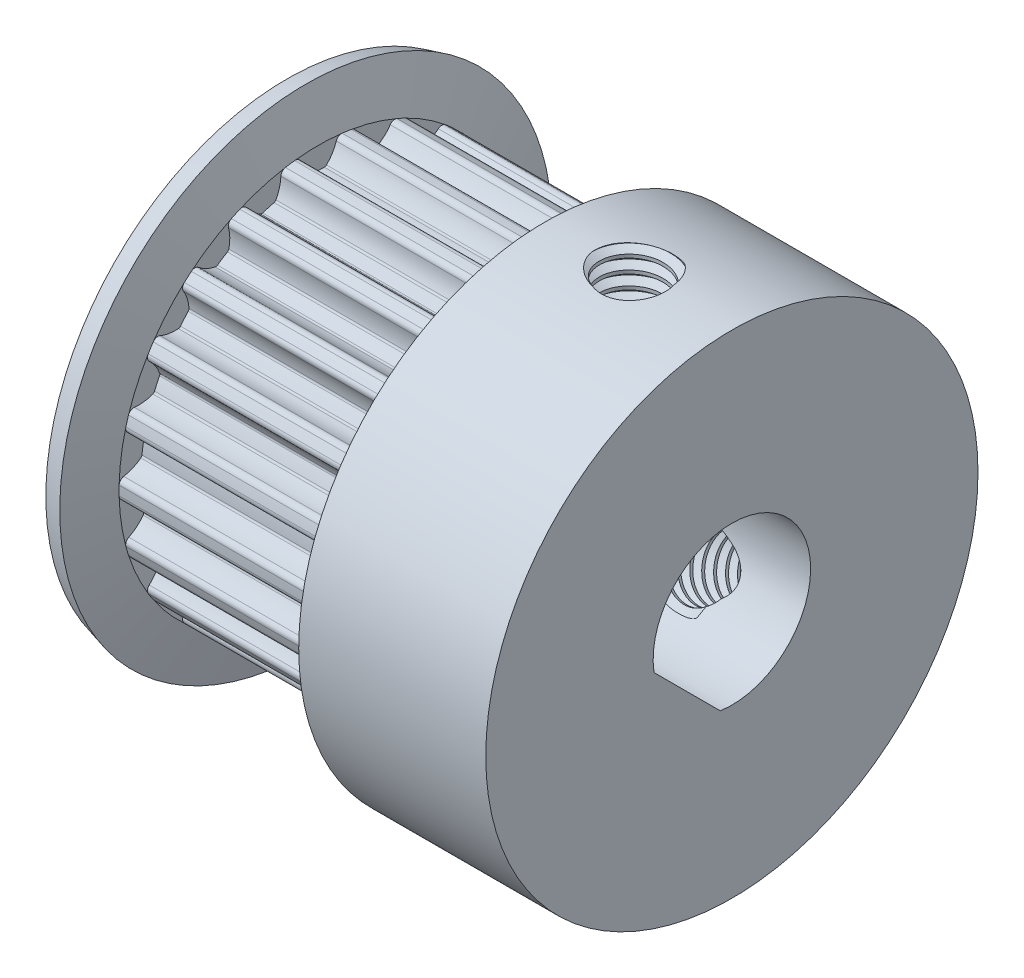
SolidWorks part; units mm, degrees
ref_plane "Front Plane" through (0, 0, 0) normal (0, 0, 1) x (1, 0, 0)
ref_plane "Top Plane" through (0, 0, 0) normal (0, 1, 0) x (1, 0, 0)
ref_plane "Right Plane" through (0, 0, 0) normal (1, 0, 0) x (0, 0, -1)
sketch "Sketch12" plane through (0, 0, 0) normal (0, 0, 1) x (1, 0, 0)
  line L0 (1, 9.9933) -> (1, 0)
  line L1 (1, 0) -> (2, 0)
  line L2 (2, 0) -> (2, 10.125)
  line L3 (2, 10.125) -> (1.3636, 12.5)
  line L4 (1.3636, 12.5) -> (0.3977, 12.2412)
  line L5 (0.3977, 12.2412) -> (1, 9.9933)
  line L6 (0.3977, 0) -> (2, 0) construction
revolve "Revolve1" add sketch "Sketch12" angle 360 about L6 reverse direction yes
other "Freeze***"
ref_plane "Plane4" through (2, 0, 0) normal (1, 0, 0) x (0, 0, -1)
sketch "Sketch16" plane through (2, 0, 0) normal (1, 0, 0) x (0, 0, -1)
  arc A0 (0.963, 10.0791) -> (1.9156, 9.9421) centre (0, 0) cw
  arc A1 (1.9156, 9.9421) -> (2.1887, 8.7453) centre (3.8823, 9.7613) ccw
  arc A2 (2.1887, 8.7453) -> (2.8868, 8.5403) centre (0, 0) cw
  arc A3 (2.8868, 8.5403) -> (3.7636, 9.3995) centre (2.0113, 10.3107) ccw
  arc A4 (3.7636, 9.3995) -> (4.6391, 8.9997) centre (0, 0) cw
  arc A5 (4.6391, 8.9997) -> (4.5639, 7.7744) centre (6.4751, 8.2721) ccw
  arc A6 (4.5639, 7.7744) -> (5.1759, 7.3811) centre (0, 0) cw
  arc A7 (5.1759, 7.3811) -> (6.2593, 7.9584) centre (4.8347, 9.3263) ccw
  arc A8 (6.2593, 7.9584) -> (6.9867, 7.3282) centre (0, 0) cw
  arc A9 (6.9867, 7.3282) -> (6.5693, 6.1737) centre (8.5434, 6.1128) ccw
  arc A10 (6.5693, 6.1737) -> (7.0458, 5.6238) centre (0, 0) cw
  arc A11 (7.0458, 5.6238) -> (8.2479, 5.8726) centre (7.2664, 7.5865) ccw
  arc A12 (8.2479, 5.8726) -> (8.7682, 5.063) centre (0, 0) cw
  arc A13 (8.7682, 5.063) -> (8.0425, 4.0728) centre (9.9195, 3.4582) ccw
  arc A14 (8.0425, 4.0728) -> (8.3448, 3.411) centre (0, 0) cw
  arc A15 (8.3448, 3.411) -> (9.5683, 3.311) centre (9.1094, 5.232) ccw
  arc A16 (9.5683, 3.311) -> (9.8395, 2.3876) centre (0, 0) cw
  arc A17 (9.8395, 2.3876) -> (8.8642, 1.642) centre (10.4919, 0.5235) ccw
  arc A18 (8.8642, 1.642) -> (8.9677, 0.9218) centre (0, 0) cw
  arc A19 (8.9677, 0.9218) -> (10.1136, 0.4812) centre (10.2144, 2.4536) ccw
  arc A20 (10.1136, 0.4812) -> (10.1136, -0.4812) centre (0, 0) cw
  arc A21 (10.1136, -0.4812) -> (8.9677, -0.9218) centre (10.2144, -2.4536) ccw
  arc A22 (8.9677, -0.9218) -> (8.8642, -1.642) centre (0, 0) cw
  arc A23 (8.8642, -1.642) -> (9.8395, -2.3876) centre (10.4919, -0.5235) ccw
  arc A24 (9.8395, -2.3876) -> (9.5683, -3.311) centre (0, 0) cw
  arc A25 (9.5683, -3.311) -> (8.3448, -3.411) centre (9.1094, -5.232) ccw
  arc A26 (8.3448, -3.411) -> (8.0425, -4.0728) centre (0, 0) cw
  arc A27 (8.0425, -4.0728) -> (8.7682, -5.063) centre (9.9195, -3.4582) ccw
  arc A28 (8.7682, -5.063) -> (8.2479, -5.8726) centre (0, 0) cw
  arc A29 (8.2479, -5.8726) -> (7.0458, -5.6238) centre (7.2664, -7.5865) ccw
  arc A30 (7.0458, -5.6238) -> (6.5693, -6.1737) centre (0, 0) cw
  arc A31 (6.5693, -6.1737) -> (6.9867, -7.3282) centre (8.5434, -6.1128) ccw
  arc A32 (6.9867, -7.3282) -> (6.2593, -7.9584) centre (0, 0) cw
  arc A33 (6.2593, -7.9584) -> (5.1759, -7.3811) centre (4.8347, -9.3263) ccw
  arc A34 (5.1759, -7.3811) -> (4.5639, -7.7744) centre (0, 0) cw
  arc A35 (4.5639, -7.7744) -> (4.6391, -8.9997) centre (6.4751, -8.2721) ccw
  arc A36 (4.6391, -8.9997) -> (3.7636, -9.3995) centre (0, 0) cw
  arc A37 (3.7636, -9.3995) -> (2.8868, -8.5403) centre (2.0113, -10.3107) ccw
  arc A38 (2.8868, -8.5403) -> (2.1887, -8.7453) centre (0, 0) cw
  arc A39 (2.1887, -8.7453) -> (1.9156, -9.9421) centre (3.8823, -9.7613) ccw
  arc A40 (1.9156, -9.9421) -> (0.963, -10.0791) centre (0, 0) cw
  arc A41 (0.963, -10.0791) -> (0.3638, -9.0077) centre (-0.975, -10.4597) ccw
  arc A42 (0.3638, -9.0077) -> (-0.3638, -9.0077) centre (0, 0) cw
  arc A43 (-0.3638, -9.0077) -> (-0.963, -10.0791) centre (0.975, -10.4597) ccw
  arc A44 (-0.963, -10.0791) -> (-1.9156, -9.9421) centre (0, 0) cw
  arc A45 (-1.9156, -9.9421) -> (-2.1887, -8.7453) centre (-3.8823, -9.7613) ccw
  arc A46 (-2.1887, -8.7453) -> (-2.8868, -8.5403) centre (0, 0) cw
  arc A47 (-2.8868, -8.5403) -> (-3.7636, -9.3995) centre (-2.0113, -10.3107) ccw
  arc A48 (-3.7636, -9.3995) -> (-4.6391, -8.9997) centre (0, 0) cw
  arc A49 (-4.6391, -8.9997) -> (-4.5639, -7.7744) centre (-6.4751, -8.2721) ccw
  arc A50 (-4.5639, -7.7744) -> (-5.1759, -7.3811) centre (0, 0) cw
  arc A51 (-5.1759, -7.3811) -> (-6.2593, -7.9584) centre (-4.8347, -9.3263) ccw
  arc A52 (-6.2593, -7.9584) -> (-6.9867, -7.3282) centre (0, 0) cw
  arc A53 (-6.9867, -7.3282) -> (-6.5693, -6.1737) centre (-8.5434, -6.1128) ccw
  arc A54 (-6.5693, -6.1737) -> (-7.0458, -5.6238) centre (0, 0) cw
  arc A55 (-7.0458, -5.6238) -> (-8.2479, -5.8726) centre (-7.2664, -7.5865) ccw
  arc A56 (-8.2479, -5.8726) -> (-8.7682, -5.063) centre (0, 0) cw
  arc A57 (-8.7682, -5.063) -> (-8.0425, -4.0728) centre (-9.9195, -3.4582) ccw
  arc A58 (-8.0425, -4.0728) -> (-8.3448, -3.411) centre (0, 0) cw
  arc A59 (-8.3448, -3.411) -> (-9.5683, -3.311) centre (-9.1094, -5.232) ccw
  arc A60 (-9.5683, -3.311) -> (-9.8395, -2.3876) centre (0, 0) cw
  arc A61 (-9.8395, -2.3876) -> (-8.8642, -1.642) centre (-10.4919, -0.5235) ccw
  arc A62 (-8.8642, -1.642) -> (-8.9677, -0.9218) centre (0, 0) cw
  arc A63 (-8.9677, -0.9218) -> (-10.1136, -0.4812) centre (-10.2144, -2.4536) ccw
  arc A64 (-10.1136, -0.4812) -> (-10.1136, 0.4812) centre (0, 0) cw
  arc A65 (-10.1136, 0.4812) -> (-8.9677, 0.9218) centre (-10.2144, 2.4536) ccw
  arc A66 (-8.9677, 0.9218) -> (-8.8642, 1.642) centre (0, 0) cw
  arc A67 (-8.8642, 1.642) -> (-9.8395, 2.3876) centre (-10.4919, 0.5235) ccw
  arc A68 (-9.8395, 2.3876) -> (-9.5683, 3.311) centre (0, 0) cw
  arc A69 (-9.5683, 3.311) -> (-8.3448, 3.411) centre (-9.1094, 5.232) ccw
  arc A70 (-8.3448, 3.411) -> (-8.0425, 4.0728) centre (0, 0) cw
  arc A71 (-8.0425, 4.0728) -> (-8.7682, 5.063) centre (-9.9195, 3.4582) ccw
  arc A72 (-8.7682, 5.063) -> (-8.2479, 5.8726) centre (0, 0) cw
  arc A73 (-8.2479, 5.8726) -> (-7.0458, 5.6238) centre (-7.2664, 7.5865) ccw
  arc A74 (-7.0458, 5.6238) -> (-6.5693, 6.1737) centre (0, 0) cw
  arc A75 (-6.5693, 6.1737) -> (-6.9867, 7.3282) centre (-8.5434, 6.1128) ccw
  arc A76 (-6.9867, 7.3282) -> (-6.2593, 7.9584) centre (0, 0) cw
  arc A77 (-6.2593, 7.9584) -> (-5.1759, 7.3811) centre (-4.8347, 9.3263) ccw
  arc A78 (-5.1759, 7.3811) -> (-4.5639, 7.7744) centre (0, 0) cw
  arc A79 (-4.5639, 7.7744) -> (-4.6391, 8.9997) centre (-6.4751, 8.2721) ccw
  arc A80 (-4.6391, 8.9997) -> (-3.7636, 9.3995) centre (0, 0) cw
  arc A81 (-3.7636, 9.3995) -> (-2.8868, 8.5403) centre (-2.0113, 10.3107) ccw
  arc A82 (-2.8868, 8.5403) -> (-2.1887, 8.7453) centre (0, 0) cw
  arc A83 (-2.1887, 8.7453) -> (-1.9156, 9.9421) centre (-3.8823, 9.7613) ccw
  arc A84 (-1.9156, 9.9421) -> (-0.963, 10.0791) centre (0, 0) cw
  arc A85 (-0.963, 10.0791) -> (-0.3638, 9.0077) centre (0.975, 10.4597) ccw
  arc A86 (-0.3638, 9.0077) -> (0.3638, 9.0077) centre (0, 0) cw
  arc A87 (0.3638, 9.0077) -> (0.963, 10.0791) centre (-0.975, 10.4597) ccw
extrude "Boss-Extrude4" add sketch "Sketch16" along normal blind 11
ref_plane "Plane5" through (13, 0, 0) normal (-1, 0, 0) x (0, 0, 1)
sketch "Sketch21" plane through (13, 0, 0) normal (-1, 0, 0) x (0, 0, 1)
  circle A0 centre (0, 0) radius 12.5
extrude "Boss-Extrude5" add sketch "Sketch21" against normal blind 10
sketch "Sketch22" plane through (1, 0, 0) normal (-1, 0, 0) x (0, 0, 1)
  circle A0 centre (0, 0) radius 8
extrude "Boss-Extrude6" add sketch "Sketch22" along normal blind 1
hole_wizard "Ø8.0 (8) Diameter Hole2" positions "Sketch24" profile "Sketch23" hole size "Ø8.0" standard "ANSI Metric"
sketch "Sketch24" plane through (23, 0, 0) normal (1, 0, 0) x (0, 0, -1)
  point P0 (0, 0)
sketch "Sketch23" plane through (23, 0, 0) normal (0, 1, 0) x (0, 0, -1)
  line L0 (0, 0) -> (0, 23)
  line L1 (0, 23) -> (4, 23)
  line L2 (4, 23) -> (4, 0)
  line L5 (4, 0) -> (0, 0)
  line L11 (0, -6.35) -> (0, 107.95) construction
  dimension "Thru Hole Dia." = 8
  dimension "Thru Hole Depth" = 23
ref_plane "Plane6" through (0, -1.8284, -3.1669) normal (0, 0.5, 0.866) x (1, 0, 0)
hole_wizard "M3 Clearance Hole3" positions "Sketch26" profile "Sketch25" hole size "M3" standard "ANSI Metric"
sketch "Sketch26" plane through (0, -1.8284, -3.1669) normal (0, 0.5, 0.866) x (1, 0, 0)
  point P0 (18, 0)
sketch "Sketch25" plane through (18, -1.8284, -3.1669) normal (1, 0, 0) x (0, -0.866, 0.5)
  line L0 (0, 0) -> (0, 13.4185)
  line L1 (0, 13.4185) -> (1.621, 13.4185)
  line L2 (1.621, 13.4185) -> (1.621, 0)
  line L5 (1.621, 0) -> (0, 0)
  line L11 (0, -6.35) -> (0, 107.95) construction
  dimension "Thru Hole Dia." = 3.242
  dimension "Thru Hole Depth" = 13.4185
ref_plane "Plane7" through (0, 3.6568, 0) normal (0, -1, 0) x (-1, 0, 0)
hole_wizard "M3 Clearance Hole4" positions "Sketch28" profile "Sketch27" hole size "M3" standard "ANSI Metric"
sketch "Sketch28" plane through (0, 3.6568, 0) normal (0, -1, 0) x (-1, 0, 0)
  point P0 (-18, 0)
sketch "Sketch27" plane through (18, 3.6568, 0) normal (1, 0, 0) x (0, 0, -1)
  line L0 (0, 0) -> (0, 8.8432)
  line L1 (0, 8.8432) -> (1.621, 8.8432)
  line L2 (1.621, 8.8432) -> (1.621, 0)
  line L5 (1.621, 0) -> (0, 0)
  line L11 (0, -6.35) -> (0, 107.95) construction
  dimension "Thru Hole Dia." = 3.242
  dimension "Thru Hole Depth" = 8.8432
chamfer "Chamfer2" distance 2 angle 14.036 1 edges at (13, 0, 12.5) first distance on face at (13, 0, 0)
fillet "Fillet3" radius 0.15 44 edges at (7.5, -7.3811, 5.1759) (7.5, -5.6238, 7.0458) (7.5, -8.5403, 2.8868) (7.5, 0.9218, 8.9677) (7.5, 0.9218, -8.9677) (7.5, 8.7453, 2.1887) (7.5, 5.6238, -7.0458) (7.5, 7.3811, -5.1759) (7.5, 1.642, -8.8642) (7.5, 8.5403, 2.8868) (7.5, -6.1737, 6.5693) (7.5, 4.0728, -8.0425) (7.5, 6.1737, -6.5693) (7.5, -3.411, -8.3448) (7.5, -7.7744, 4.5639) (7.5, -0.9218, 8.9677) (7.5, 7.7744, -4.5639) (7.5, -4.0728, -8.0425) (7.5, -8.7453, 2.1887) (7.5, -1.642, 8.8642) (7.5, -7.3811, -5.1759) (7.5, 6.1737, 6.5693) (7.5, -7.7744, -4.5639) (7.5, 3.411, -8.3448) (7.5, 4.0728, 8.0425) (7.5, 5.6238, 7.0458) (7.5, 3.411, 8.3448) (7.5, 8.7453, -2.1887) (7.5, -8.5403, -2.8868) (7.5, -5.6238, -7.0458) (7.5, -8.7453, -2.1887) (7.5, -3.411, 8.3448) (7.5, 7.7744, 4.5639) (7.5, -6.1737, -6.5693) (7.5, 7.3811, 5.1759) (7.5, -4.0728, 8.0425) (7.5, -9.0077, -0.3638) (7.5, 9.0077, -0.3638) (7.5, -9.0077, 0.3638) (7.5, 8.5403, -2.8868) (7.5, -1.642, -8.8642) (7.5, 9.0077, 0.3638) (7.5, -0.9218, -8.9677) (7.5, 1.642, 8.8642) tangent propagation no
fillet "Fillet4" radius 0.28 44 edges at (7.5, -3.311, 9.5683) (7.5, -9.9421, 1.9156) (7.5, -7.9584, 6.2593) (7.5, 9.9421, -1.9156) (7.5, -0.4812, 10.1136) (7.5, 10.0791, -0.963) (7.5, -5.8726, 8.2479) (7.5, 9.3995, -3.7636) (7.5, -9.3995, 3.7636) (7.5, 10.0791, 0.963) (7.5, 0.4812, 10.1136) (7.5, 8.9997, -4.6391) (7.5, -2.3876, 9.8395) (7.5, 9.9421, 1.9156) (7.5, -5.063, 8.7682) (7.5, 7.9584, -6.2593) (7.5, -7.3282, 6.9867) (7.5, 9.3995, 3.7636) (7.5, -8.9997, 4.6391) (7.5, 7.3282, -6.9867) (7.5, -10.0791, 0.963) (7.5, 8.9997, 4.6391) (7.5, -2.3876, -9.8395) (7.5, 5.8726, -8.2479) (7.5, -3.311, -9.5683) (7.5, 7.9584, 6.2593) (7.5, -5.063, -8.7682) (7.5, 5.063, -8.7682) (7.5, -5.8726, -8.2479) (7.5, 7.3282, 6.9867) (7.5, -7.3282, -6.9867) (7.5, 3.311, -9.5683) (7.5, -7.9584, -6.2593) (7.5, 5.8726, 8.2479) (7.5, -8.9997, -4.6391) (7.5, 2.3876, -9.8395) (7.5, -9.3995, -3.7636) (7.5, 5.063, 8.7682) (7.5, -9.9421, -1.9156) (7.5, 0.4812, -10.1136) (7.5, -10.0791, -0.963) (7.5, 3.311, 9.5683) (7.5, -0.4812, -10.1136) (7.5, 2.3876, 9.8395) tangent propagation no
ref_plane "Plane8" through (0, 12.5, 0) normal (0, 1, 0) x (1, 0, 0)
thread "Thread1" pitch 0.7 method cut profile "Thread Profile1" start angle 0, offset 1, length 10, pitch 0.7, diameter 3.242
ref_plane "Plane9" through (16.379, 13.5, 0) normal (0, 0, 1) x (-1, 0, 0)
sketch "Thread Profile1" plane through (16.379, 13.5, 0) normal (0, 0, 1) x (-1, 0, 0)
  line L0 (0, 0) -> (0, 0.7) construction
  line L1 (0, 0) -> (0.3789, 0.2187)
  line L2 (0.3789, 0.2187) -> (0.3789, 0.3062)
  line L3 (0.3789, 0.3062) -> (0, 0.525)
  line L4 (0.3789, 0.2625) -> (0, 0.2625) construction
  line L11 (0, 0) -> (0, 0.525)
  point P2 (0, 0)
  dimension "Pitch" = 0.7
  dimension "Profile_Angle" = 60
  dimension "Profile_Land" = 0.0875
  dimension "Profile_Height" = 0.3789
ref_axis "Axis1" through (18, 12.5, 0) along (0, -1, 0)
ref_axis "Axis2" through (18, -6.9605, -12.056) along (0, 0.5, 0.866)
ref_plane "Plane11" through (0, -6.25, -10.8253) normal (0, -0.5, -0.866) x (-1, 0, 0)
thread "Thread2" pitch 0.7 method cut profile "Thread Profile2" start angle 0, offset 1, length 10, pitch 0.7, diameter 3.242
ref_plane "Plane12" through (19.621, -6.75, -11.6913) normal (0, -0.866, 0.5) x (1, 0, 0)
sketch "Thread Profile2" plane through (19.621, -6.75, -11.6913) normal (0, -0.866, 0.5) x (1, 0, 0)
  line L0 (0, 0) -> (0, 0.7) construction
  line L1 (0, 0) -> (0.3789, 0.2187)
  line L2 (0.3789, 0.2187) -> (0.3789, 0.3062)
  line L3 (0.3789, 0.3062) -> (0, 0.525)
  line L4 (0.3789, 0.2625) -> (0, 0.2625) construction
  line L11 (0, 0) -> (0, 0.525)
  point P2 (0, 0)
  dimension "Pitch" = 0.7
  dimension "Profile_Angle" = 60
  dimension "Profile_Land" = 0.0875
  dimension "Profile_Height" = 0.3789
sketch "Sketch35" plane through (0, 0, 0) normal (-1, 0, 0) x (0, 0, 1)
  line L0 (3.9564, -0.5889) -> (0.5889, -3.9564)
  arc A0 (0.5889, -3.9564) -> (3.9564, -0.5889) centre (0, 0) ccw
extrude "Boss-Extrude7" add sketch "Sketch35" against normal up to surface (23 mm away) up to face at (23, 0, -4)
